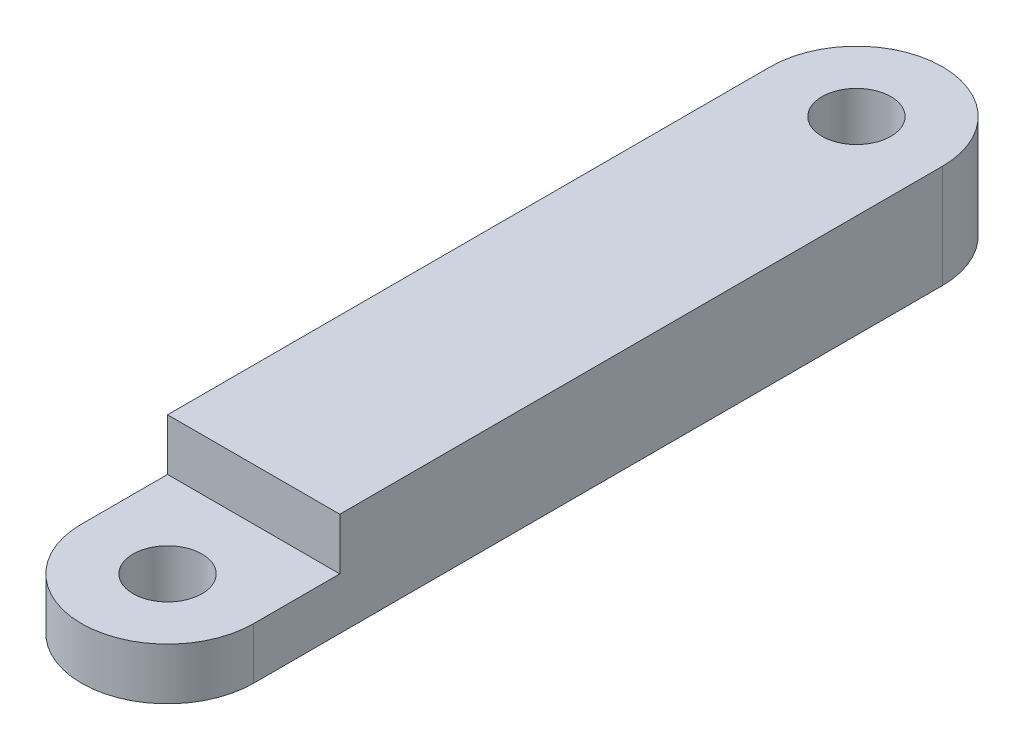
SolidWorks part; units mm, degrees
ref_plane "Plan de face" through (0, 0, 0) normal (0, 0, 1) x (1, 0, 0)
ref_plane "Plan de dessus" through (0, 0, 0) normal (0, 1, 0) x (1, 0, 0)
ref_plane "Plan de droite" through (0, 0, 0) normal (1, 0, 0) x (0, 0, -1)
sketch "Esquisse1" plane through (0, 0, 0) normal (0, 1, 0) x (1, 0, 0)
  line L0 (0, 0) -> (0, -40) construction
  line L1 (-5, -40) -> (-5, 0)
  line L2 (5, -40) -> (5, 0)
  circle A0 centre (0, 0) radius 2
  arc A1 (5, 0) -> (-5, 0) centre (0, 0) ccw
  circle A2 centre (0, -40) radius 2
  arc A4 (-5, -40) -> (5, -40) centre (0, -40) ccw
  dimension "D1" = 4
  dimension "D2" = 10
  dimension "D3" = 4
  dimension "D5" = 40
extrude "Boss.-Extru.1" add sketch "Esquisse1" along normal blind 3 and the other way blind 3 contours L1 L2 A1 A0 A2 region at (0, 0, 20)
sketch "Esquisse2" plane through (0, 3, 0) normal (0, 1, 0) x (1, 0, 0)
  line L0 (5, -35) -> (-5, -35)
  line L1 (5, -40) -> (5, 0) construction
  line L2 (-5, -40) -> (-5, 0) construction
  line L3 (5, -35) -> (5, -46.0416)
  line L4 (5, -46.0416) -> (-5, -46.0416)
  line L5 (-5, -46.0416) -> (-5, -35)
  circle A0 centre (0, -40) radius 5 construction
  arc A2 (-5, -40) -> (5, -40) centre (0, -40) ccw construction
extrude "Enlèv. mat.-Extru.1" cut sketch "Esquisse2" against normal blind 3
